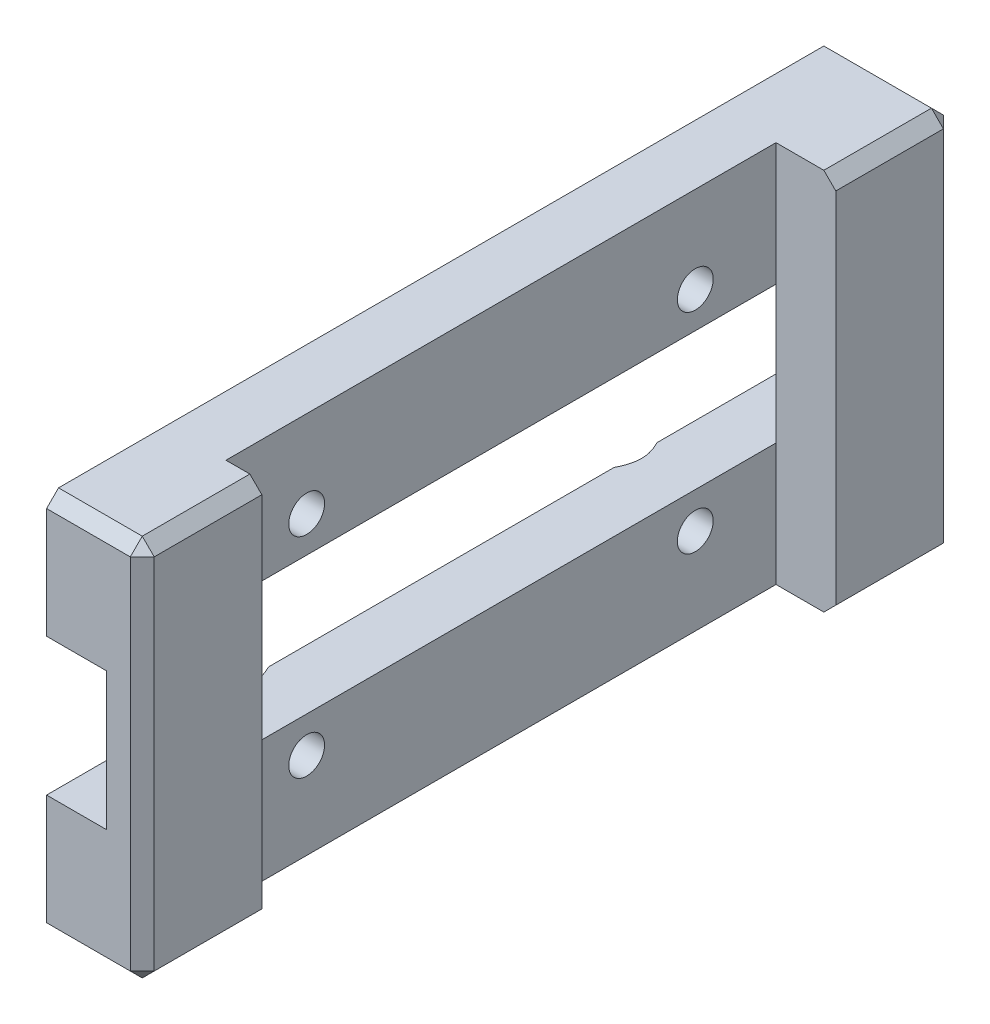
SolidWorks part; units mm, degrees
ref_plane "前视基准面" through (0, 0, 0) normal (0, 0, 1) x (1, 0, 0)
ref_plane "上视基准面" through (0, 0, 0) normal (0, 1, 0) x (1, 0, 0)
ref_plane "右视基准面" through (0, 0, 0) normal (1, 0, 0) x (0, 0, -1)
sketch "草图2" plane through (0, 0, 0) normal (1, 0, 0) x (0, 0, -1)
  line L1 (33, -16) -> (-33, -16)
  line L2 (33, -16) -> (33, 16)
  line L3 (33, 16) -> (-33, 16)
  line L4 (-33, -16) -> (-33, 16)
  line L5 (33, -16) -> (-33, 16) construction
  line L6 (33, 16) -> (-33, -16) construction
  point P0 (0, 0)
  dimension "D1" = 66
  dimension "D2" = 32
extrude "凸台-拉伸1" add sketch "草图2" along normal blind 5
sketch "草图3" plane through (0, 0, 0) normal (-1, 0, 0) x (0, 0, 1)
  line L1 (23, -5.75) -> (-23, -5.75)
  line L2 (23, -5.75) -> (23, 5.75)
  line L3 (23, 5.75) -> (-23, 5.75)
  line L4 (-23, -5.75) -> (-23, 5.75)
  line L5 (23, -5.75) -> (-23, 5.75) construction
  line L6 (23, 5.75) -> (-23, -5.75) construction
  line L7 (-33, -16) -> (-33, 16) construction
  point P0 (0, 0)
  point P8 (0, 0)
  point P9 (0, 0)
  dimension "D1" = 11.5
  dimension "D2" = 10
extrude "切除-拉伸2" cut sketch "草图3" against normal through all
sketch "草图4" plane through (0, 0, -33) normal (0, 0, -1) x (-1, 0, 0)
  line L0 (0, -16) -> (0, 16) construction
  line L1 (0, -5.75) -> (-5, -5.75)
  line L2 (0, -5.75) -> (0, 5.75)
  line L3 (0, 5.75) -> (-5, 5.75)
  line L4 (-5, -5.75) -> (-5, 5.75)
  line L5 (0, -5.75) -> (-5, 5.75) construction
  line L6 (0, 5.75) -> (-5, -5.75) construction
  line L7 (-5, 0) -> (0, 0) construction
  line L8 (-5, -16) -> (-5, 16) construction
  point P0 (-2.5, 0)
  point P12 (0, 0)
  dimension "D1" = 11.5
  dimension "D2" = 5
extrude "切除-拉伸3" cut sketch "草图4" against normal through all
sketch "草图5" plane through (5, 0, 0) normal (1, 0, 0) x (0, 0, -1)
  line L0 (33, 16) -> (-33, 16) construction
  line L1 (33, -16) -> (23, -16)
  line L2 (33, -16) -> (33, 16)
  line L3 (33, 16) -> (23, 16)
  line L4 (23, -16) -> (23, 16)
  line L5 (33, -16) -> (23, 16) construction
  line L6 (33, 16) -> (23, -16) construction
  line L7 (-33, -16) -> (33, -16) construction
  line L8 (33, 5.75) -> (33, 16) construction
  point P0 (28, 0)
  dimension "D1" = 10
extrude "凸台-拉伸2" add sketch "草图5" along normal blind 5
sketch "草图6" plane through (5, 0, 0) normal (1, 0, 0) x (0, 0, -1)
  line L0 (23, 16) -> (-33, 16) construction
  line L1 (-23, -16) -> (-33, -16)
  line L2 (-23, -16) -> (-23, 16)
  line L3 (-23, 16) -> (-33, 16)
  line L4 (-33, -16) -> (-33, 16)
  line L5 (-23, -16) -> (-33, 16) construction
  line L6 (-23, 16) -> (-33, -16) construction
  line L7 (-33, 16) -> (-33, 5.75) construction
  line L8 (-33, -16) -> (23, -16) construction
  point P0 (-28, 0)
  dimension "D1" = 10
extrude "凸台-拉伸3" add sketch "草图6" along normal blind 3
sketch "草图7" plane through (0, 0, 0) normal (-1, 0, 0) x (0, 0, 1)
  line L0 (0, 16) -> (0, -16) construction
  line L1 (-33, 16) -> (33, 16) construction
  line L2 (33, -16) -> (-33, -16) construction
  line L3 (-32.9554, 0) -> (32.9768, 0) construction
  circle A0 centre (-16.25, 8.75) radius 1.5
  circle A1 centre (16.25, 8.75) radius 1.5
  circle A2 centre (16.25, -8.75) radius 1.5
  circle A3 centre (-16.25, -8.75) radius 1.5
  point P17 (0, 0)
  point P18 (0, 0)
  point P19 (0, 0)
  dimension "D1" = 3
  dimension "D2" = 32.5
  dimension "D3" = 17.5
extrude "切除-拉伸4" cut sketch "草图7" against normal through all
chamfer "倒角1" distance 2 angle 45 4 edges at (0, -8.75, 17.75) (0, -8.75, -14.75) (0, 8.75, -14.75) (0, 8.75, 17.75)
chamfer "倒角2" distance 1 angle 45 10 edges at (8, 0, 33) (10, 0, -33) (8, -16, 28) (8, 16, 28) (10, -16, -28) (10, 16, -28) (4, -16, 33) (4, 16, 33) (5, -16, -33) (5, 16, -33)
